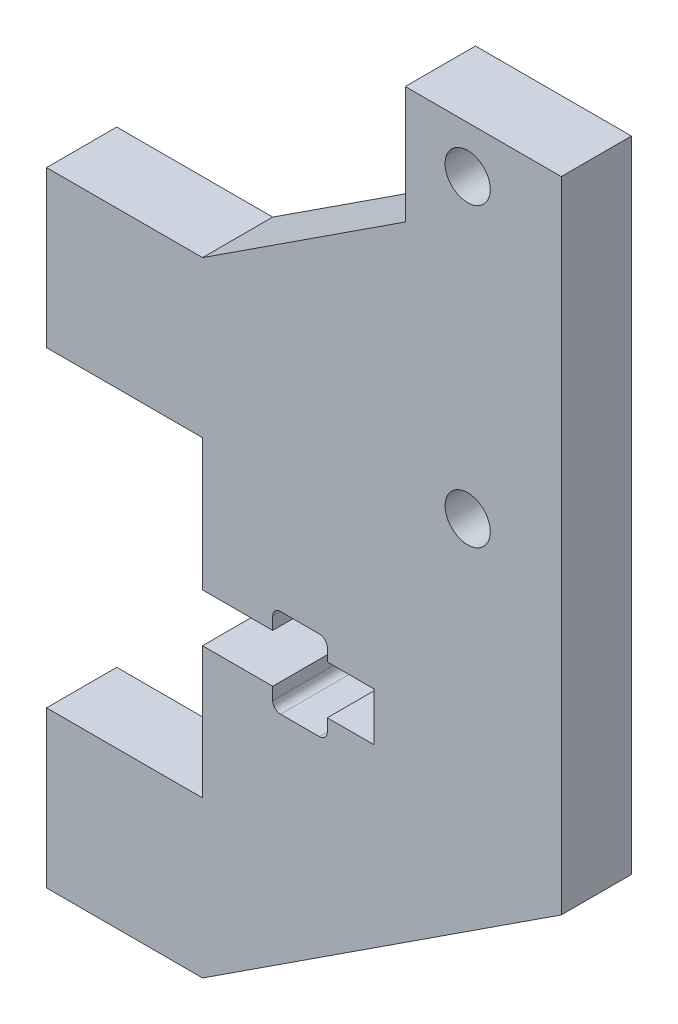
SolidWorks part; units mm, degrees
ref_plane "Front Plane" through (0, 0, 0) normal (0, 0, 1) x (1, 0, 0)
ref_plane "Top Plane" through (0, 0, 0) normal (0, 1, 0) x (1, 0, 0)
ref_plane "Right Plane" through (0, 0, 0) normal (1, 0, 0) x (0, 0, -1)
sketch "Sketch1" plane through (0, 0, 0) normal (0, 0, 1) x (1, 0, 0)
  line L0 (13, 3.4783) -> (0, -5)
  line L1 (0, -5) -> (-10, -5)
  line L2 (-10, -5) -> (-10, -15)
  line L3 (-10, -15) -> (0, -15)
  line L4 (0, -15) -> (0, -35)
  line L5 (0, -35) -> (-10, -35)
  line L6 (-10, -35) -> (-10, -45)
  line L7 (-10, -45) -> (0, -45)
  line L10 (0, -45) -> (23, -30)
  line L11 (23, -30) -> (23, 11)
  line L12 (23, 11) -> (13, 11)
  line L13 (13, 11) -> (13, 3.4783)
  line L15 (0, -5) -> (0, -45) construction
  line L16 (-10, -10) -> (0, -10) construction
  line L17 (-10, -40) -> (0, -40) construction
  line L18 (-10, -15) -> (-10, -35) construction
  line L19 (-10, -25) -> (0, -25) construction
  dimension "D1" = 10
  dimension "D2" = 10
  dimension "D3" = 10
  dimension "D4" = 10
  dimension "D5" = 15
  dimension "D8" = 10
  dimension "D10" = 13
  dimension "D6" = 15
  dimension "D7" = 16
extrude "Boss-Extrude1" add sketch "Sketch1" along normal blind 4.5
sketch "Sketch2" plane through (0, 0, 4.5) normal (0, 0, 1) x (1, 0, 0)
  line L0 (0, -25) -> (23, -25) construction
  line L1 (0, -15) -> (0, -35) construction
  line L3 (11, -26.55) -> (11, -23.45) construction
  line L4 (11, -23.45) -> (0, -23.45) construction
  line L5 (0, -26.55) -> (0, -23.45)
  line L6 (0, -23.45) -> (4.5, -23.45)
  line L7 (4.5, -23.45) -> (4.5, -22.65)
  line L8 (5, -22.15) -> (7.5, -22.15)
  line L9 (8, -22.65) -> (8, -23.45)
  line L10 (8, -23.45) -> (11, -23.45)
  line L11 (11, -23.45) -> (11, -26.55)
  line L12 (11, -26.55) -> (0, -26.55) construction
  line L13 (8, -26.55) -> (11, -26.55)
  line L14 (8, -27.35) -> (8, -26.55)
  line L15 (5, -27.85) -> (7.5, -27.85)
  line L16 (4.5, -26.55) -> (4.5, -27.35)
  line L17 (0, -26.55) -> (4.5, -26.55)
  line L18 (23, -30) -> (23, 11) construction
  arc A0 (7.5, -22.15) -> (8, -22.65) centre (7.5, -22.65) cw
  arc A1 (4.5, -22.65) -> (5, -22.15) centre (5, -22.65) cw
  arc A2 (4.5, -27.35) -> (5, -27.85) centre (5, -27.35) ccw
  arc A3 (7.5, -27.85) -> (8, -27.35) centre (7.5, -27.35) ccw
  point P15 (8, -22.15)
  point P18 (4.5, -22.15)
  point P27 (11, -25)
  point P29 (4.5, -27.85)
  point P30 (8, -27.85)
  dimension "D6" = 0.5
  dimension "D1" = 11
  dimension "D2" = 1.55
  dimension "D3" = 8
  dimension "D4" = 3.5
  dimension "D5" = 2.85
extrude "screw-cutout" cut sketch "Sketch2" against normal through all
sketch "Sketch3" plane through (0, 0, 4.5) normal (0, 0, 1) x (1, 0, 0)
  line L0 (17, 55) -> (17, -45) construction
  line L3 (13, 11) -> (13, 3.4783) construction
  line L5 (-10, -45) -> (0, -45) construction
  line L10 (11, -26.55) -> (11, -23.45) construction
  circle A1 centre (17, 8) radius 1.45
  circle A5 centre (17, -11) radius 1.45
  point P8 (11, -25)
  dimension "D4" = 2.9
  dimension "D11" = 2.9
  dimension "D6" = 4
  dimension "D12" = 19
  dimension "D2" = 14
extrude "Cut-Extrude2" cut sketch "Sketch3" against normal through all
sketch "Sketch4" [suppressed] plane through (0, 0, 4.5) normal (0, 0, 1) x (1, 0, 0)
  line L0 (17, -11) -> (17, 8) construction
  line L1 (17, -1.5) -> (13, -1.5) construction
  line L2 (13, 11) -> (13, 3.4783) construction
  line L4 (15, 2.5) -> (13, 2.5)
  line L5 (15, 2.5) -> (15, -5.5)
  line L6 (15, -5.5) -> (13, -5.5)
  line L7 (13, 2.5) -> (13, -5.5)
  line L8 (15, 2.5) -> (13, -5.5) construction
  line L9 (15, -5.5) -> (13, 2.5) construction
  circle A1 centre (17, 8) radius 1.55 construction
  circle A3 centre (17, -11) radius 1.55 construction
  point P11 (14, -1.5)
  dimension "D1" = 8
  dimension "D2" = 2
  dimension "D3" = 3
equation "\"X-ROD-SPACING\"=45"
equation "\"Y-ROD-SPACING\"=75"
equation "\"Z-ROD-SPACING\"=17.5"
equation "\"Y-BED-OFFSET\"=2"
equation "\"Y-BED-ROD-INSET\"=3.5"
equation "\"T-SLOT-NUT-FILLET-RADIUS\"=0.5"
equation "\"T-SLOT-SCREW-SHAFT-RADIUS\"=1.55"
equation "\"T-SLOT-SCREW-SHAFT-CUTOUT-LENGTH\"=11"
equation "\"T-SLOT-NUT-DEPTH\"=3.5"
equation "\"T-SLOT-NUT-WIDTH\"=2.85"
equation "\"T-SLOT-NUT-END-DISTANCE\"=8"
equation "\"ACRYLIC-THICKNESS\"=10"
equation "\"ACRYLIC-THICKNESS2\"=4.5"
equation "\"ACRYLIC-TAB-CUTOUT-SIZE\"=\"ACRYLIC-THICKNESS\"+\"ACRYLIC-TAB-TOLERANCE\"*2"
equation "\"ACRYLIC-TAB-WIDTH\"=\"ACRYLIC-THICKNESS\""
equation "\"ACRYLIC-M3-HOLE\"=2.9"
equation "\"SMOOTHROD-CAP-SCREW-DISTANCE\"=20"
equation "\"FRAME-WIDTH-INNER\"=370"
equation "\"NEMA17-HOLE-SPACING\"=31"
equation "\"NEMA17-CENTRAL-CUTOUT\"=22.5"
equation "\"Z-BRACKET-REACH\"=55"
equation "\"Z-ROD-INSET\"=13.5"
equation "\"TOP-BRACKET-SPACING\"=40"
equation "\"SMOOTHROD-X-LENGTH\"=350"
equation "\"SMOOTHROD-Y-LENGTH\"=350"
equation "\"SMOOTHROD-Z-LENGTH\"=350"
equation "\"SMOOTHROD-TIGHTENING-HEADROOM\"=.25"
equation "\"LEADSCREW-Z-LENGTH\"=300"
equation "\"SCREW-LENGTH-FRAME\"=\"ACRYLIC-THICKNESS\" + 10"
equation "\"SCREW-HEAD-RADIUS\"=6"
equation "\"PRINTED-X-SMOOTHROD-DIAMETER\"=8.8"
equation "\"PRINTED-X-SMOOTHROD-CUTOUT\"=10"
equation "\"PRINTED-X-BASE-HEIGHT\"=10"
equation "\"PRINTED-LM8UU-CUTOUT-SIZE\"=15.5"
equation "\"PRINTED-LM8UU-CUTOUT-LENGTH\"=24.5"
equation "\"PRINTED-X-IDLER-HEIGHT\"=16"
equation "\"PSU-MOUNTING-WIDTH\"=95"
equation "\"PSU-MOUNTING-HEIGHT\"=177"
equation "\"Y-BELT-TO-ROD-DISTANCE\"=20"
equation "\"SPOOL-HOLDER-ROD-SPACING\"=150"
equation "\"D1@Sketch1\"=\"ACRYLIC-TAB-WIDTH\""
equation "\"D2@Sketch1\"=\"ACRYLIC-TAB-WIDTH\""
equation "\"D3@Sketch1\"=\"ACRYLIC-THICKNESS\""
equation "\"D4@Sketch1\"=\"ACRYLIC-THICKNESS\""
equation "\"D1@Boss-Extrude1\"=\"ACRYLIC-THICKNESS2\""
equation "\"D1@Sketch2\"=\"T-SLOT-SCREW-SHAFT-CUTOUT-LENGTH\""
equation "\"D2@Sketch2\"=\"T-SLOT-SCREW-SHAFT-RADIUS\""
equation "\"D3@Sketch2\"=\"T-SLOT-NUT-END-DISTANCE\""
equation "\"D4@Sketch2\"=\"T-SLOT-NUT-DEPTH\""
equation "\"D5@Sketch2\"=\"T-SLOT-NUT-WIDTH\""
equation "\"D6@Sketch2\"=\"T-SLOT-NUT-FILLET-RADIUS\""
equation "\"D4@Sketch3\"=\"ACRYLIC-M3-HOLE\""
equation "\"D11@Sketch3\"=\"ACRYLIC-M3-HOLE\""
equation "\"Y-BED-SCREW-SPACING\"=209"
equation "\"Y-BED-SCREW-CUTOUT-SLOT-HEIGHT\"=2"
equation "\"ACRYLIC-TAB-TOLERANCE\"=-.05"
equation "\"SCREW-LENGTH-MOTOR\"=\"ACRYLIC-THICKNESS\" + 5"
equation "\"SCREW-LENGTH-EXTRUDER\"=28"
equation "\"PRINTED-M3-HOLE\"=3.5"
equation "\"ACRYLIC-X-CARRIAGE-WIDTH\"=55"
equation "\"ACRYLIC-X-CARRIAGE-HEIGHT\"=75"
equation "\"ACRYLIC-X-CARRIAGE-LM8UU-CUTOUT-WIDTH\"=24.25"
equation "\"ACRYLIC-X-CARRIAGE-LM8UU-CUTOUT-HEIGHT\"=11.0"
equation "\"ACRYLIC-X-CARRIAGE-SCREW-SPACING-X\"=15"
equation "\"ACRYLIC-X-CARRIAGE-SCREW-SPACING-Y\"=33"
equation "\"ACRYLIC-X-CARRIAGE-CENTER-TAB-SPACING\"=14"
equation "\"ACRYLIC-X-CARRIAGE-EXTRUDER-OFFSET\"=26"
equation "\"ACRYLIC-X-CARRIAGE-EXTRUDER-ANGLE\"=90"
equation "\"ACRYLIC-X-CARRIAGE-EXTRUDER-SHELF-DEPTH\"=\"ACRYLIC-X-CARRIAGE-EXTRUDER-OFFSET\" + 28"
equation "\"ACRYLIC-X-CARRIAGE-EXTRUDER-BRACE-SPACING\"=23"
equation "\"ACRYLIC-X-CARRIAGE-EXTRUDER-BRACE-TAB-OFFSET\"=20"
equation "\"ACRYLIC-X-CARRIAGE-EXTRUDER-BRACE-HEIGHT\"=35"
equation "\"ACRYLIC-X-CARRIAGE-EXTRUDER-BRACE-SCREW-SPACING\"=22"
equation "\"ACRYLIC-X-CARRIAGE-DUAL-WIDTH-MULTIPLIER\"=1.65"
equation "\"ACRYLIC-X-CARRIAGE-DUAL-HOTEND-SPACING\"=42"
equation "\"ACRYLIC-X-CARRIAGE-DUAL-WIDTH\"=75"
equation "\"ACRYLIC-X-CARRIAGE-DUAL-HOTEND-SEPARATION\"=36"
equation "\"ACRYLIC-X-CARRIAGE-DUAL-MOUNT-PLATE-DEPTH\"=75"
equation "\"ACRYLIC-X-CARRIAGE-DUAL-MOUNT-BRACE-WIDTH\"=33"
equation "\"ACRYLIC-X-CARRIAGE-DUAL-MOUNT-SCREW-WIDTH\"=40"
equation "\"BLOWER-FAN-WIDTH\"=15"
